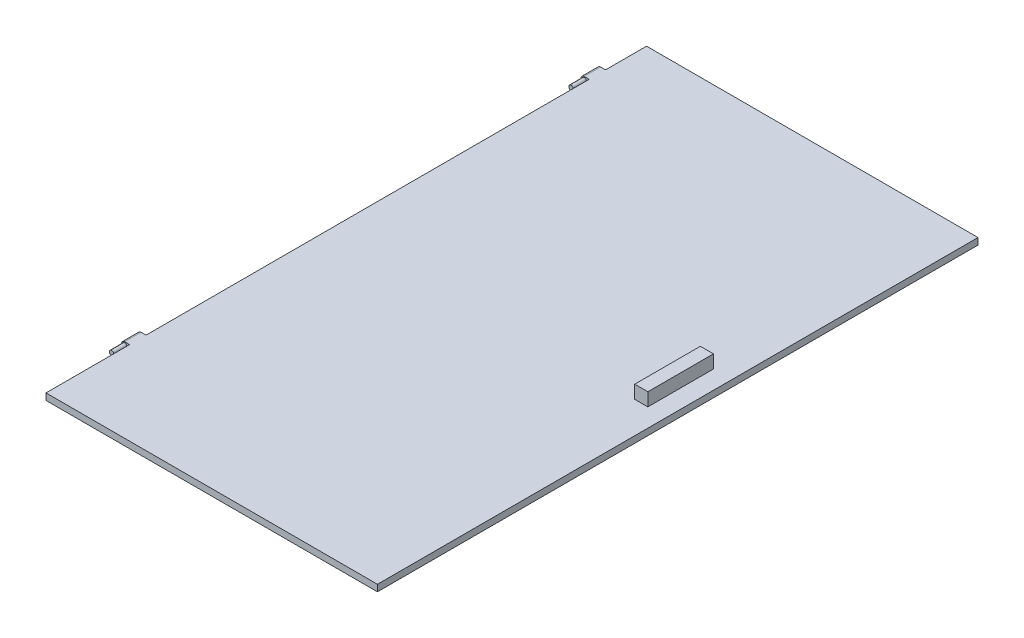
SolidWorks part; units mm, degrees
material "ABS PC"
ref_plane "Front Plane" through (0, 0, 0) normal (0, 0, 1) x (1, 0, 0)
ref_plane "Top Plane" through (0, 0, 0) normal (0, 1, 0) x (1, 0, 0)
ref_plane "Right Plane" through (0, 0, 0) normal (1, 0, 0) x (0, 0, -1)
sketch "Sketch1" plane through (0, 0, 0) normal (0, 1, 0) x (1, 0, 0)
  line L1 (245, -490) -> (-260, -490)
  line L2 (245, -490) -> (245, 425)
  line L3 (245, 425) -> (-260, 425)
  line L4 (-260, -490) -> (-260, 425)
  point P0 (0, 0)
  dimension "D1" = 490
  dimension "D2" = 505
  dimension "D3" = 425
extrude "Boss-Extrude1" add sketch "Sketch1" along normal blind 10
sketch "Sketch2" plane through (-260, 0, 0) normal (-1, 0, 0) x (0, 0, 1)
  line L0 (-425, 10) -> (490, 10) construction
  line L1 (-362.5, 0) -> (-337.5, 0)
  line L2 (-362.5, 0) -> (-362.5, 10)
  line L3 (-362.5, 10) -> (-337.5, 10)
  line L4 (-337.5, 0) -> (-337.5, 10)
  line L5 (-362.5, 0) -> (-337.5, 10) construction
  line L6 (-362.5, 10) -> (-337.5, 0) construction
  line L7 (0, 50.5566) -> (0, -38.8043) construction
  line L8 (362.5, 0) -> (362.5, 10)
  line L9 (337.5, 0) -> (337.5, 10)
  line L10 (362.5, 10) -> (337.5, 10)
  line L11 (362.5, 0) -> (337.5, 0)
  line L12 (-425, 0) -> (490, 0) construction
  point P0 (-350, 5)
  dimension "D1" = 337.5
  dimension "D2" = 25
extrude "Boss-Extrude2" add sketch "Sketch2" along normal blind 12.5
sketch "Sketch3" plane through (0, 0, -337.5) normal (0, 0, 1) x (1, 0, 0)
  line L0 (-272.5, 0) -> (-272.5, 10) construction
  line L2 (-272.5, 10) -> (-260, 10) construction
  circle A0 centre (-267.5, 5) radius 3.5
  point P6 (-273.311, 10)
  dimension "D1" = 7
  dimension "D2" = 5
  dimension "D3" = 5
extrude "Boss-Extrude3" add sketch "Sketch3" along normal blind 20
pattern_linear "LPattern1" count 2 spacing 700 along (0, 0, 1) of "Boss-Extrude3"
fillet "Fillet1" radius 5 4 edges at (-272.5, 0, 350) (-272.5, 10, 350) (-272.5, 0, -350) (-272.5, 10, -350)
sketch "Sketch4" plane through (0, 10, 0) normal (0, 1, 0) x (1, 0, 0)
  line L0 (-344.7756, 0) -> (524.2744, 0) construction
  line L1 (216.9612, -50) -> (196.9612, -50)
  line L2 (216.9612, -50) -> (216.9612, 50)
  line L3 (216.9612, 50) -> (196.9612, 50)
  line L4 (196.9612, -50) -> (196.9612, 50)
  line L5 (216.9612, -50) -> (196.9612, 50) construction
  line L6 (216.9612, 50) -> (196.9612, -50) construction
  point P0 (206.9612, 0)
  point P5 (0, 0)
  dimension "D1" = 100
  dimension "D2" = 20
extrude "Boss-Extrude4" add sketch "Sketch4" along normal blind 20
